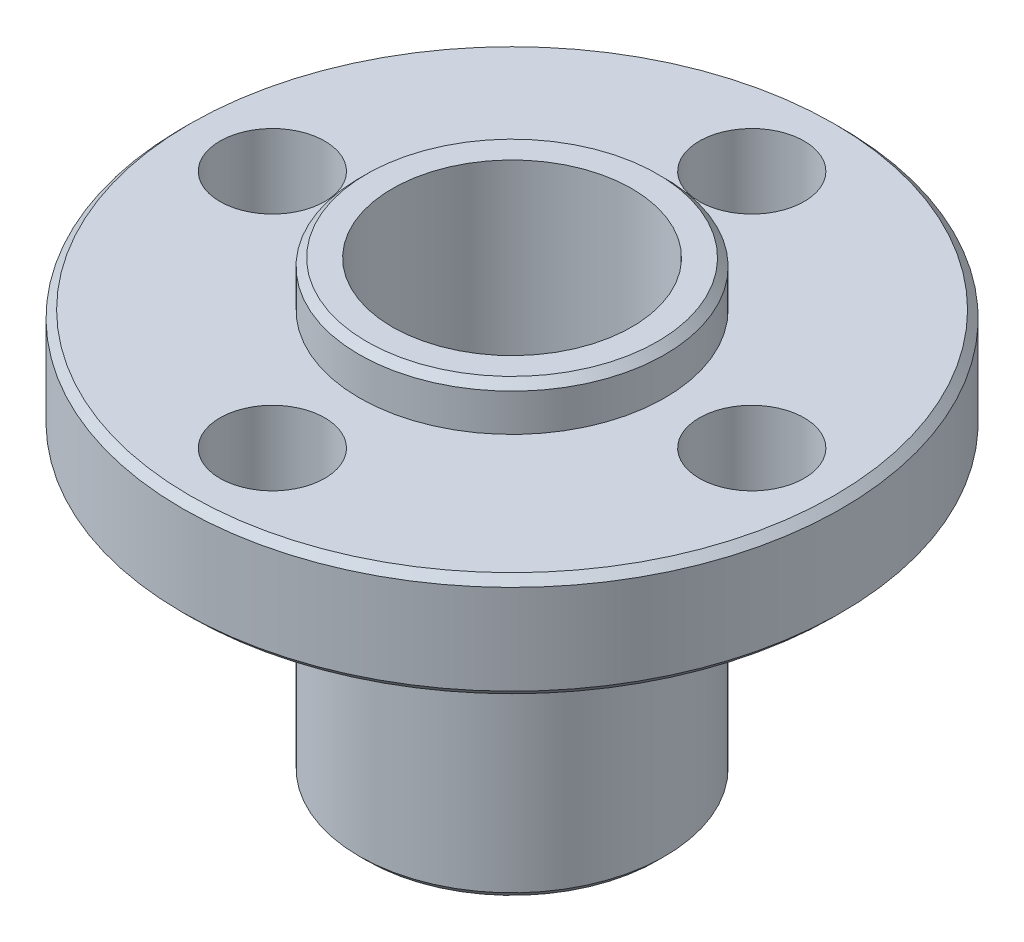
SolidWorks part; units mm, degrees
material "Aluminum Bronze"
ref_plane "Front Plane" through (0, 0, 0) normal (0, 0, 1) x (1, 0, 0)
ref_plane "Top Plane" through (0, 0, 0) normal (0, 1, 0) x (1, 0, 0)
ref_plane "Right Plane" through (0, 0, 0) normal (1, 0, 0) x (0, 0, -1)
sketch "Sketch1" plane through (0, 0, 0) normal (0, 1, 0) x (1, 0, 0)
  circle A0 centre (0, 0) radius 4
  circle A1 centre (0, 0) radius 11
  circle A2 centre (0, 0) radius 8 construction
  circle A3 centre (0, 0) radius 5.1
  circle A4 centre (0, 8) radius 1.75
  circle A5 centre (8, 0) radius 1.75
  circle A6 centre (0, -8) radius 1.75
  circle A7 centre (-8, 0) radius 1.75
  point P8 (7.9444, 0.9414)
  point P9 (-8, 0)
  point P17 (0, 0)
  dimension "D1" = 22
  dimension "D2" = 8
  dimension "D3" = 16
  dimension "D4" = 10.2
  dimension "D5" = 3.5
  dimension "D6" = 4
extrude "Boss-Extrude1" add sketch "Sketch1" along normal mid plane 3.5 contours A1 | A3 | A4 | A5 | A6 | A7
extrude "Boss-Extrude2" add sketch "Sketch1<3>" along normal blind 3.25 and the other way blind 11.75 contours A3 | A0
sketch "Sketch1<3>" plane through (0, 0, 0) normal (0, 1, 0) x (1, 0, 0) same geometry as "Sketch1"
chamfer "Chamfer1" distance 0.25 angle 45 4 edges at (0, -11.75, 5.1) (0, -1.75, 11) (0, 1.75, 11) (0, 3.25, 5.1)
